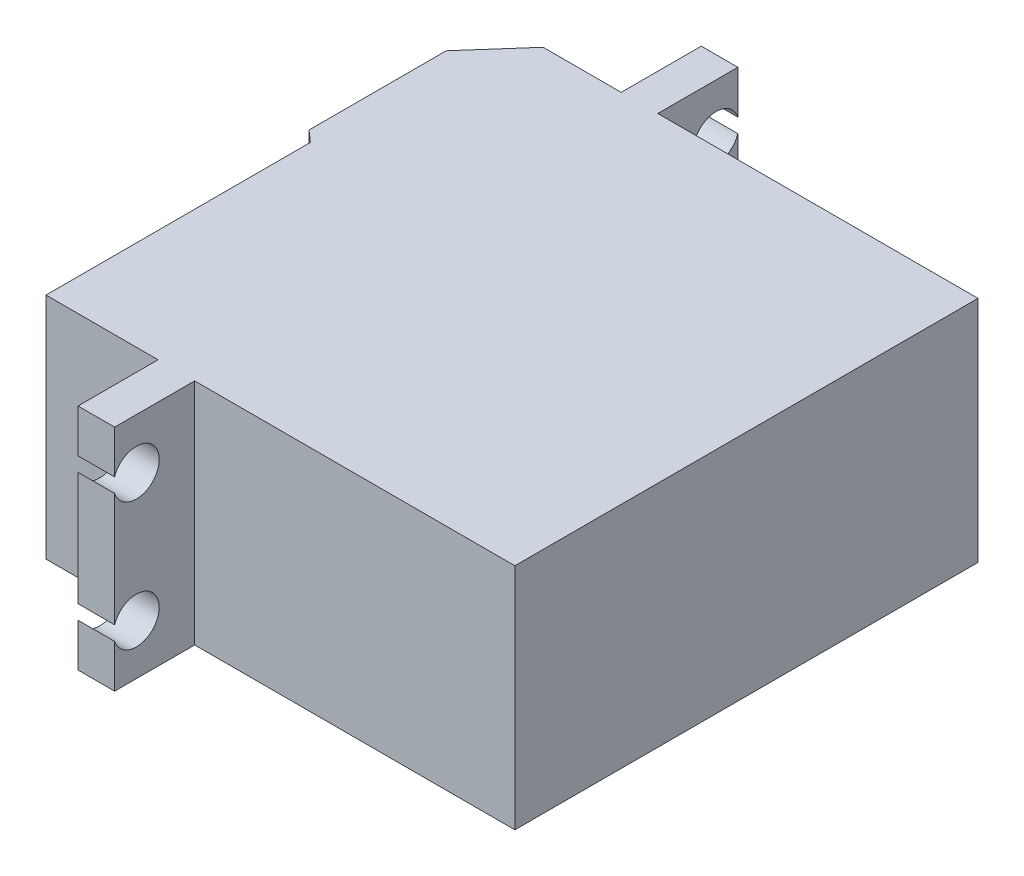
SolidWorks part; units mm, degrees
ref_plane "Front" through (0, 0, 0) normal (0, 0, 1) x (1, 0, 0)
ref_plane "Top" through (0, 0, 0) normal (0, 1, 0) x (1, 0, 0)
ref_plane "Right" through (0, 0, 0) normal (1, 0, 0) x (0, 0, -1)
sketch "Sketch1" plane through (0, 0, 0) normal (0, 1, 0) x (1, 0, 0)
  line L0 (0, 0) -> (0, 40.5)
  line L1 (0, 40.5) -> (-28, 40.5)
  line L2 (-28, 40.5) -> (-28, 47.5)
  line L3 (-28, 47.5) -> (-31.2, 47.5)
  line L4 (-31.2, 47.5) -> (-31.2, 40.5)
  line L5 (-31.2, 40.5) -> (-38.0314, 40.5)
  line L6 (-38.0314, 40.5) -> (-42, 36)
  line L7 (-42, 36) -> (-42, 24)
  line L8 (-42, 24) -> (-41, 23.1181)
  line L9 (-41, 23.1181) -> (-41, 0)
  line L10 (-41, 0) -> (-31.2, 0)
  line L11 (-31.2, 0) -> (-31.2, -7)
  line L12 (-31.2, -7) -> (-28, -7)
  line L13 (-28, -7) -> (-28, 0)
  line L14 (-28, 0) -> (0, 0)
  line L16 (-48, 33) -> (-42, 33) construction
  line L17 (-48, 33) -> (-48, 27) construction
  line L18 (-48, 27) -> (-42, 27) construction
  line L19 (-42, 33) -> (-42, 27) construction
  point P16 (-42, 30)
  point P17 (-48, 30)
  dimension "D1" = 41
  dimension "D2" = 40.5
  dimension "D3" = 7
  dimension "D4" = 28
  dimension "D5" = 3.2
  dimension "D6" = 1
  dimension "D7" = 12
  dimension "D8" = 6
  dimension "D9" = 27
  dimension "D10" = 6
extrude "Boss-Extrude1" add sketch "Sketch1" along normal blind 20
sketch "Sketch2" plane through (-42, 0, 0) normal (-1, 0, 0) x (0, 0, 1)
  line L0 (-30, 0) -> (-30, 20) construction
  line L1 (-33.4641, 10) -> (-31.7321, 7)
  line L2 (-31.7321, 7) -> (-28.2679, 7)
  line L3 (-28.2679, 7) -> (-26.5359, 10)
  line L4 (-26.5359, 10) -> (-28.2679, 13)
  line L5 (-28.2679, 13) -> (-31.7321, 13)
  line L6 (-31.7321, 13) -> (-33.4641, 10)
  line L7 (-36, 0) -> (-24, 0) construction
  line L8 (-36, 20) -> (-24, 20) construction
  line L9 (-36, 10) -> (-24, 10) construction
  line L10 (-36, 20) -> (-36, 0) construction
  line L11 (-24, 20) -> (-24, 0) construction
  circle A0 centre (-30, 10) radius 3 construction
  point P21 (-30, 10)
  dimension "D1" = 6
extrude "Boss-Extrude2" add sketch "Sketch2" along normal blind 4
sketch "Sketch3" plane through (-31.2, 0, 0) normal (-1, 0, 0) x (0, 0, 1)
  line L0 (-47.5, 10) -> (7, 10) construction
  line L1 (-47.5, 20) -> (-47.5, 0) construction
  line L2 (7, 20) -> (7, 0) construction
  line L3 (-20.25, 10) -> (-20.25, 20) construction
  line L4 (-23.1181, 20) -> (0, 20) construction
  line L5 (-47.5, 0) -> (-40.5, 0) construction
  circle A0 centre (-45.6, 4.4) radius 2
  circle A1 centre (-45.6, 15.6) radius 2
  circle A2 centre (5.1, 15.6) radius 2
  circle A3 centre (5.1, 4.4) radius 2
  dimension "D1" = 4
  dimension "D2" = 1.9
  dimension "D3" = 4.4
extrude "Cut-Extrude1" cut sketch "Sketch3" against normal through all
sketch "Sketch4" plane through (-46, 0, 0) normal (-1, 0, 0) x (0, 0, 1)
  line L0 (-26.5359, 10) -> (-33.4641, 10) construction
  circle A0 centre (-30, 10) radius 1.5
  point P6 (0, 0)
  point P7 (-30, 10)
  dimension "D1" = 3
extrude "Cut-Extrude2" cut sketch "Sketch4" against normal blind 2
equation "\"`27\"=27.8853"
equation "\"`0.1\"=2"
